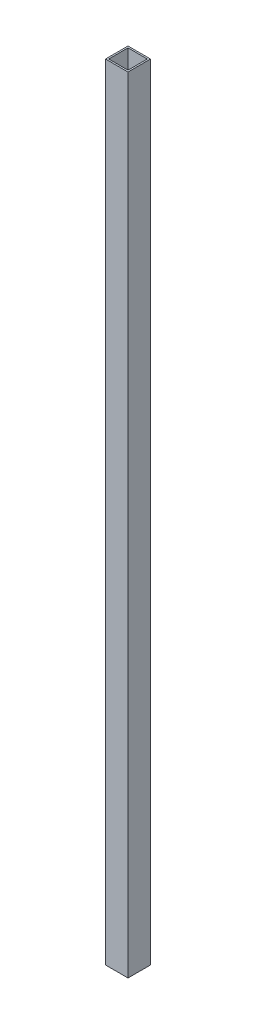
SolidWorks part; units mm, degrees
material "6061 Alloy"
ref_plane "Front Plane" through (0, 0, 0) normal (0, 0, 1) x (1, 0, 0)
ref_plane "Top Plane" through (0, 0, 0) normal (0, 1, 0) x (1, 0, 0)
ref_plane "Right Plane" through (0, 0, 0) normal (1, 0, 0) x (0, 0, -1)
sketch "Sketch1" plane through (0, 0, 0) normal (0, 1, 0) x (1, 0, 0)
  line L1 (-8.5, 8.5) -> (8.5, 8.5)
  line L2 (-8.5, 8.5) -> (-8.5, -8.5)
  line L3 (-8.5, -8.5) -> (8.5, -8.5)
  line L4 (8.5, 8.5) -> (8.5, -8.5)
  line L5 (-8.5, 8.5) -> (8.5, -8.5) construction
  line L6 (-8.5, -8.5) -> (8.5, 8.5) construction
  line L7 (-7.3, 7.3) -> (7.3, 7.3)
  line L8 (-7.3, 7.3) -> (-7.3, -7.3)
  line L9 (-7.3, -7.3) -> (7.3, -7.3)
  line L10 (7.3, 7.3) -> (7.3, -7.3)
  line L11 (-7.3, 7.3) -> (7.3, -7.3) construction
  line L12 (-7.3, -7.3) -> (7.3, 7.3) construction
  point P0 (0, 0)
  point P6 (0, 0)
  dimension "D1" = 14.6
  dimension "D2" = 17
extrude "Boss-Extrude1" add sketch "Sketch1" along normal blind 592.5 contours L1 L4 L3 L2 | L9 L10 L7 L8
